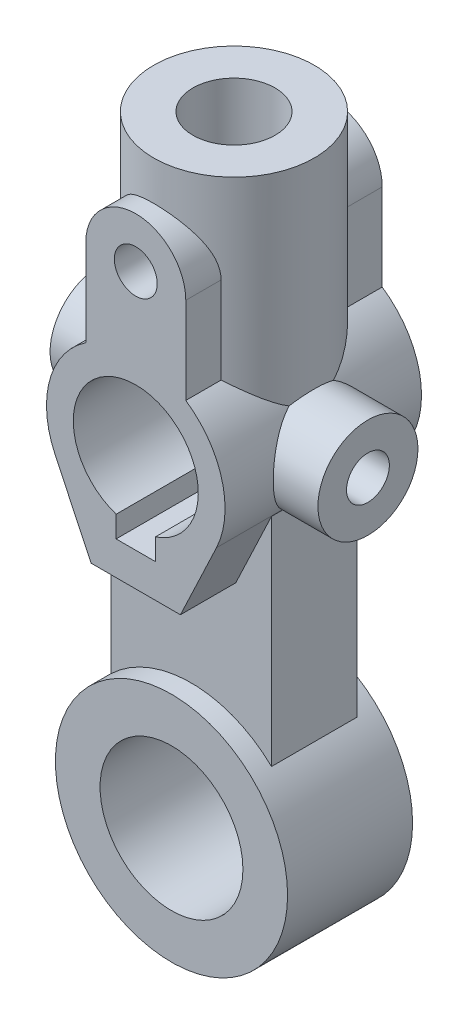
SolidWorks part; units mm, degrees
ref_plane "Front" through (0, 0, 0) normal (0, 0, 1) x (1, 0, 0)
ref_plane "Top" through (0, 0, 0) normal (0, 1, 0) x (1, 0, 0)
ref_plane "Right" through (0, 0, 0) normal (1, 0, 0) x (0, 0, -1)
sketch "Sketch_Front" plane through (0, 0, 0) normal (0, 0, 1) x (1, 0, 0)
  line L0 (0, 0) -> (0, 45) construction
  line L1 (14, 20.7123) -> (14, 45)
  line L2 (-14, 20.7123) -> (-14, 45)
  line L3 (-12.5, -32) -> (12.5, -32)
  line L4 (12.5, -32) -> (22.5914, -10.7065)
  line L5 (-12.5, -32) -> (-22.5914, -10.7065)
  line L6 (0, 0) -> (0, -32) construction
  line L7 (0, 0) -> (0, -22.6132) construction
  line L8 (-5.5, -22.6132) -> (5.5, -22.6132)
  line L9 (5.5, -22.6132) -> (5.5, -16.6132)
  line L10 (-5.5, -22.6132) -> (-5.5, -16.6132)
  arc A0 (22.5914, -10.7065) -> (14, 20.7123) centre (0, 0) ccw
  arc A1 (-14, 45) -> (14, 45) centre (0, 45) cw
  arc A2 (-14, 20.7123) -> (-22.5914, -10.7065) centre (0, 0) ccw
  circle A3 centre (0, -95) radius 32.5
  arc A4 (5.5, -16.6132) -> (-5.5, -16.6132) centre (0, 0) ccw
  circle A5 centre (0, 45) radius 6
  circle A6 centre (0, -95) radius 20
  dimension "D1" = 14
  dimension "D2" = 45
  dimension "D3" = 50
  dimension "D4" = 32
  dimension "D6" = 65
  dimension "D7" = 95
  dimension "D8" = 17.5
  dimension "D11" = 12
  dimension "D12" = 40
  dimension "D5" = 25
  dimension "D9" = 6
  dimension "D10" = 11
sketch "Sketch_Top" plane through (0, 0, 0) normal (0, 1, 0) x (1, 0, 0)
  line L0 (0, 0) -> (22.5, 0) construction
  line L1 (-22.5, 12) -> (22.5, 12)
  line L2 (-22.5, 12) -> (-22.5, -12)
  line L3 (-22.5, -12) -> (22.5, -12)
  line L4 (22.5, 12) -> (22.5, -12)
  circle A0 centre (0, 0) radius 22.5
  circle A1 centre (0, 0) radius 11.5
  dimension "D1" = 45
  dimension "D3" = 23
  dimension "D2" = 24
sketch "Sketch_Right" plane through (0, 0, 0) normal (1, 0, 0) x (0, 0, -1)
  circle A0 centre (0, 0) radius 14
  circle A1 centre (0, 0) radius 6
  dimension "D1" = 28
  dimension "D2" = 12
extrude "Boss-Extrude1" add sketch "Sketch_Front" along normal mid plane 55 contours A1 L1 A0 L4 L3 L5 A2 L2
extrude "Boss-Extrude2" add sketch "Sketch_Front<3>" along normal mid plane 35 separate body contours A3 A6 region at (-31.5808, -95, 0)
sketch "Sketch_Front<3>" plane through (0, 0, 0) normal (0, 0, 1) x (1, 0, 0) same geometry as "Sketch_Front"
extrude "Boss-Extrude3" add sketch "Sketch_Top" against normal up to surface (71.5479 mm away) contours L4 L3 L2 L1 up to face at (32.5, -95, 17.5)
extrude "Boss-Extrude4" add sketch "Sketch_Top<3>" along normal blind 70 contours A0
sketch "Sketch_Top<3>" plane through (0, 0, 0) normal (0, 1, 0) x (1, 0, 0) same geometry as "Sketch_Top"
extrude "Boss-Extrude5" add sketch "Sketch_Right" along normal mid plane 75 contours A0
extrude "Cut-Extrude1" cut sketch "Sketch_Front<4>" against normal through all and the other way through all contours L9 A4 L10 L8 | A5 region at (0, -1.1586, 0) region at (0, 45, 0)
sketch "Sketch_Front<4>" plane through (0, 0, 0) normal (0, 0, 1) x (1, 0, 0) same geometry as "Sketch_Front"
extrude "Cut-Extrude2" cut sketch "Sketch_Right<3>" against normal through all and the other way through all contours A1
sketch "Sketch_Right<3>" plane through (0, 0, 0) normal (1, 0, 0) x (0, 0, -1) same geometry as "Sketch_Right"
extrude "Cut-Extrude3" cut sketch "Sketch_Top<4>" along normal through all contours A1 region at (0, 0, 0)
sketch "Sketch_Top<4>" plane through (0, 0, 0) normal (0, 1, 0) x (1, 0, 0) same geometry as "Sketch_Top"
